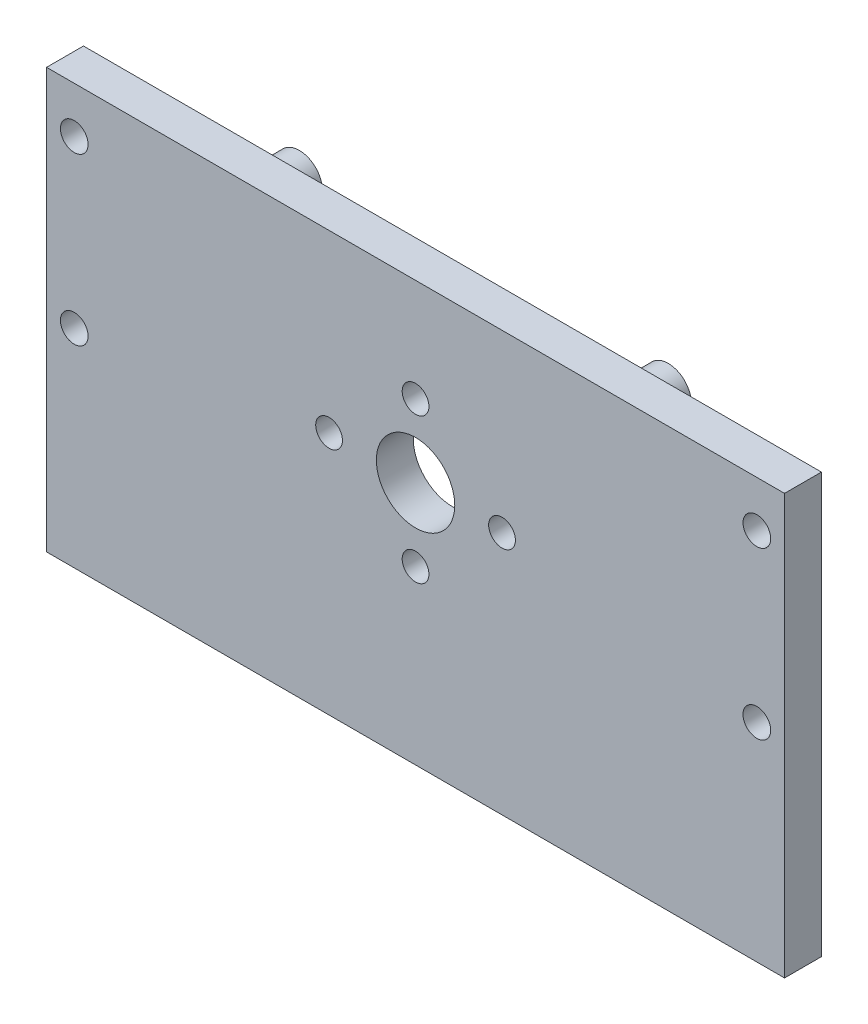
SolidWorks part; units mm, degrees
ref_plane "Front Plane" through (0, 0, 0) normal (0, 0, 1) x (1, 0, 0)
ref_plane "Top Plane" through (0, 0, 0) normal (0, 1, 0) x (1, 0, 0)
ref_plane "Right Plane" through (0, 0, 0) normal (1, 0, 0) x (0, 0, -1)
sketch "Sketch2" plane through (0, 0, 0) normal (0, 0, 1) x (1, 0, 0)
  line L0 (0, 22.75) -> (0, -22.75) construction
  line L1 (-40, 22.75) -> (40, 22.75)
  line L2 (-40, 22.75) -> (-40, -22.75)
  line L3 (-40, -22.75) -> (40, -22.75)
  line L4 (40, 22.75) -> (40, -22.75)
  line L5 (0, -22.75) -> (0, 22.75) construction
  line L6 (-40, 0) -> (40, 0) construction
  line L13 (-18.6, 18.75) -> (-18.6, 16.6788) construction
  line L14 (18.6, 18.75) -> (18.6, 16.6788) construction
  line L25 (18.5941, -7.6953) -> (40, -7.6953) construction
  line L26 (18.5941, -7.6953) -> (-18.6059, -7.6953)
  line L27 (18.5941, -7.6953) -> (18.5941, -11.6953)
  line L28 (18.5941, -11.6953) -> (-18.6059, -11.6953)
  line L29 (-18.6059, -7.6953) -> (-18.6059, -11.6953)
  circle A0 centre (0, 3.75) radius 4.25
  circle A2 centre (37, 17.75) radius 1.5
  circle A3 centre (37, -0.25) radius 1.5
  circle A4 centre (-37, -0.25) radius 1.5
  circle A5 centre (-37, 17.75) radius 1.5
  circle A6 centre (-20, 18.75) radius 2.5
  circle A7 centre (20, 18.75) radius 2.5
  circle A8 centre (-20, -19.25) radius 2.5
  circle A9 centre (20, -19.25) radius 2.5
  circle A10 centre (20, 18.75) radius 1.4
  circle A11 centre (20, -19.25) radius 1.4
  circle A12 centre (-20, 18.75) radius 1.4
  circle A14 centre (-20, -19.25) radius 1.4
  circle A17 centre (-8.7186, 12.4686) radius 1.5
  circle A18 centre (-8.7186, 12.4686) radius 2.5
  circle A19 centre (8.7186, 12.4686) radius 1.5
  circle A20 centre (8.7186, 12.4686) radius 2.5
  circle A21 centre (8.7186, -4.9686) radius 1.5
  circle A22 centre (8.7186, -4.9686) radius 2.5
  circle A23 centre (-8.7186, -4.9686) radius 1.5
  circle A24 centre (-8.7186, -4.9686) radius 2.5
  point P0 (0, 0)
  dimension "D4" = 8.5
  dimension "D6" = 3
  dimension "D7" = 3
  dimension "D8" = 3
  dimension "D9" = 3
  dimension "D10" = 3
  dimension "D14" = 5
  dimension "D15" = 5
  dimension "D16" = 5
  dimension "D17" = 5
  dimension "D18" = 2.8
  dimension "D19" = 2.8
  dimension "D20" = 2.8
  dimension "D21" = 20
  dimension "D22" = 2.8
  dimension "D23" = 20
  dimension "D27" = 4
  dimension "D28" = 3
  dimension "D29" = 5
  dimension "D30" = 3
  dimension "D31" = 5
  dimension "D32" = 3
  dimension "D33" = 5
  dimension "D34" = 3
  dimension "D35" = 5
  dimension "D1" = 45.5
  dimension "D2" = 80
  dimension "D5" = 26.5
  dimension "D11" = 5
  dimension "D12" = 3
  dimension "D13" = 18
  dimension "D24" = 38
  dimension "D25" = 4
  dimension "D26" = 4
  dimension "D36" = 37.2
  dimension "D37" = 10.2814
  dimension "D38" = 17.7814
  dimension "D39" = 17.7814
  dimension "D40" = 31.2814
  dimension "D41" = 31.2814
extrude "Boss-Extrude5" add sketch "Sketch2" along normal blind 3 and the other way blind 1 contours L4 L1 L2 L3 A24 A22 A20 A18 A9 A8 A7 A6 A5 A4 A3 A2 A0 L29 L26 L27 L28 | A6 A12 | A12 | A18 A17 | A17 | A20 A19 | A19 | A24 A23 | A23 | A22 A21 | A21 | A7 A10 | A10 | L26 L29 L28 L27 | A11 | A9 A11 | A14 | A8 A14 region at (0, 21.8297, 0) region at (-0.0059, -9.6953, 0) region at (-22.4293, 18.75, 0) region at (17.5707, 18.75, 0) region at (-22.4293, -19.25, 0) region at (17.5707, -19.25, 0) region at (20, 18.75, 0) region at (20, -19.25, 0) region at (-20, 18.75, 0) region at (-20, -19.25, 0) region at (-8.7186, 12.4686, 0) region at (-11.1479, 12.4686, 0) region at (8.7186, 12.4686, 0) region at (6.2894, 12.4686, 0) region at (8.7186, -4.9686, 0) region at (6.2894, -4.9686, 0) region at (-8.7186, -4.9686, 0) region at (-11.1479, -4.9686, 0)
extrude "Boss-Extrude6" add sketch "Sketch2<8>" against normal blind 4.4 contours A7 A10 | A6 A12 | A8 A14 | L26 L29 L28 L27 | A9 A11 region at (-0.0059, -9.6953, 0) region at (-22.4293, 18.75, 0) region at (17.5707, 18.75, 0) region at (-22.4293, -19.25, 0) region at (17.5707, -19.25, 0)
sketch "Sketch2<8>" plane through (0, 0, 0) normal (0, 0, 1) x (1, 0, 0) same geometry as "Sketch2"
sketch "Sketch6" plane through (0, 0, -1) normal (0, 0, -1) x (-1, 0, 0)
sketch "Sketch7" plane through (0, 0, -1) normal (0, 0, -1) x (-1, 0, 0)
  line L0 (0, 8) -> (0, -0.5) construction
  line L1 (-4.25, 3.75) -> (4.25, 3.75) construction
  line L2 (0, 3.75) -> (9.375, 3.75)
  line L3 (9.375, 3.75) -> (0, 3.75)
  line L4 (0, 3.75) -> (-9.375, 3.75) construction
  line L5 (0, 3.75) -> (0, 11.625) construction
  line L6 (0, 3.75) -> (0, -4.125) construction
  circle A0 centre (0, 3.75) radius 4.25 construction
  circle A1 centre (0, -4.125) radius 1.45
  circle A2 centre (9.375, 3.75) radius 1.45
  circle A3 centre (0, 11.625) radius 1.45
  circle A4 centre (-9.375, 3.75) radius 1.45
  dimension "D1" = 9.375
  dimension "D5" = 2.9
  dimension "D6" = 2.9
  dimension "D7" = 2.9
  dimension "D8" = 2.9
  dimension "D2" = 9.375
  dimension "D3" = 7.875
  dimension "D4" = 7.875
extrude "Cut-Extrude3" cut sketch "Sketch7" against normal through all contours A1 | A4 | A3 | A2
fillet "Fillet1" radius 1 4 edges at (22.5, -19.25, -1) (-17.5, -19.25, -1) (-17.5, 18.75, -1) (22.5, 18.75, -1)
